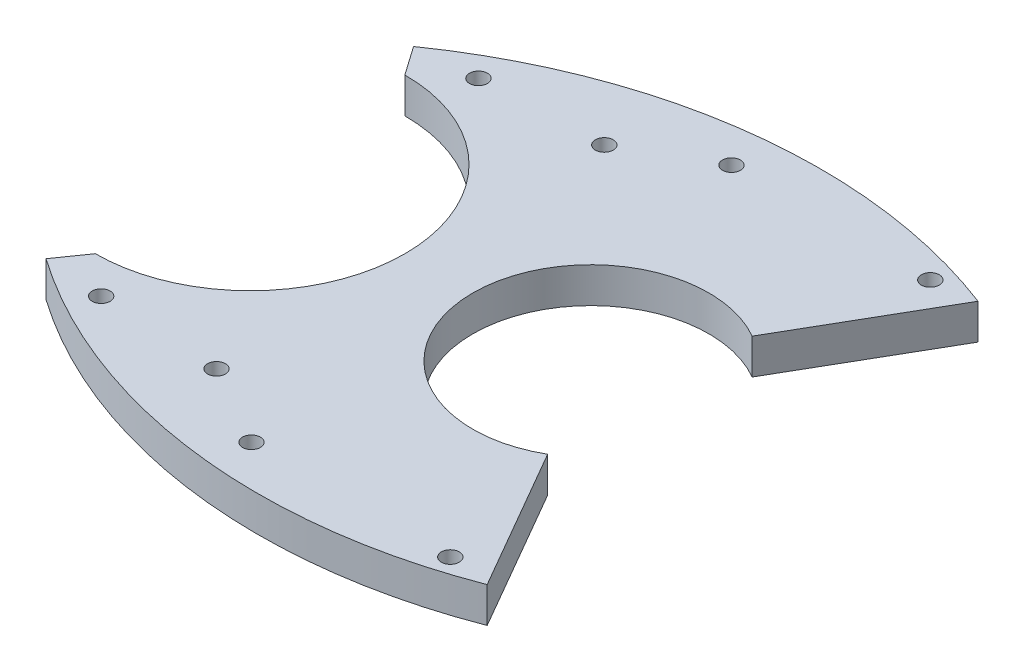
SolidWorks part; units mm, degrees
material "Alloy Steel"
ref_plane "Front Plane" through (0, 0, 0) normal (0, 0, 1) x (1, 0, 0)
ref_plane "Top Plane" through (0, 0, 0) normal (0, 1, 0) x (1, 0, 0)
ref_plane "Right Plane" through (0, 0, 0) normal (1, 0, 0) x (0, 0, -1)
sketch "Sketch2" plane through (0, 0, 0) normal (0, 1, 0) x (1, 0, 0)
  line L0 (78.375, 27.4963) -> (100.6, 65.9911)
  line L1 (78.375, -27.4963) -> (100.6, -65.9911)
  line L2 (62.5, 0) -> (12.5, 0) construction
  line L3 (12.5, 0) -> (0, 0) construction
  line L4 (62.5, 0) -> (101.5469, 0) construction
  line L5 (0, 0) -> (-29.1377, 41.6129) construction
  line L6 (0, 0) -> (-29.1377, -41.6129) construction
  line L7 (-29.1377, 41.6129) -> (-34.601, 49.4153)
  line L8 (-29.1377, -41.6129) -> (-34.601, -49.4153)
  line L9 (62.5, 0) -> (89.2304, 64.533) construction
  line L10 (62.5, 0) -> (35.7696, 64.533) construction
  line L13 (0, 0) -> (13.9698, 52.1358) construction
  line L14 (0, 0) -> (-18.4605, 50.7199) construction
  arc A0 (78.375, 27.4963) -> (78.375, -27.4963) centre (62.5, 0) ccw
  arc A1 (-34.601, 49.4153) -> (100.6, 65.9911) centre (48.58, -69.3794) cw
  arc A2 (-34.601, -49.4153) -> (100.6, -65.9911) centre (48.58, 69.3794) ccw
  arc A3 (-29.1377, 41.6129) -> (-29.1377, -41.6129) centre (-29.1129, 0) cw
  circle A4 centre (-18.4605, 50.7199) radius 2.413
  circle A5 centre (13.9698, 52.1358) radius 2.413
  circle A8 centre (35.7696, 64.533) radius 2.413
  circle A9 centre (89.2304, 64.533) radius 2.413
  circle A12 centre (89.2304, -64.533) radius 2.413
  circle A13 centre (35.7696, -64.533) radius 2.413
  circle A14 centre (13.9698, -52.1358) radius 2.413
  circle A15 centre (-18.4605, -50.7199) radius 2.413
  point P32 (0, 0)
  point P33 (0, 0)
  point P34 (0, 0)
  point P35 (54.5611, 0)
  point P36 (0, 0)
  dimension "D2" = 31.75
  dimension "D11" = 4.826
  dimension "D1" = 60
  dimension "D3" = 76.2
  dimension "D4" = 60
  dimension "D5" = 50
  dimension "D6" = 12.5
  dimension "D7" = 55
  dimension "D8" = 55
  dimension "D9" = 50.8
  dimension "D10" = 9.525
  dimension "D12" = 69.85
  dimension "D13" = 45
  dimension "D14" = 53.975
  dimension "D15" = 75
  dimension "D16" = 110
extrude "Boss-Extrude1" add sketch "Sketch2" along normal mid plane 9.525
ref_axis "Turbine Axis" through (0, 5.2388, 0) along (0, -1, 0)
ref_axis "Pump Axis" through (62.5, 4.7625, 0) along (0, -1, 0)
